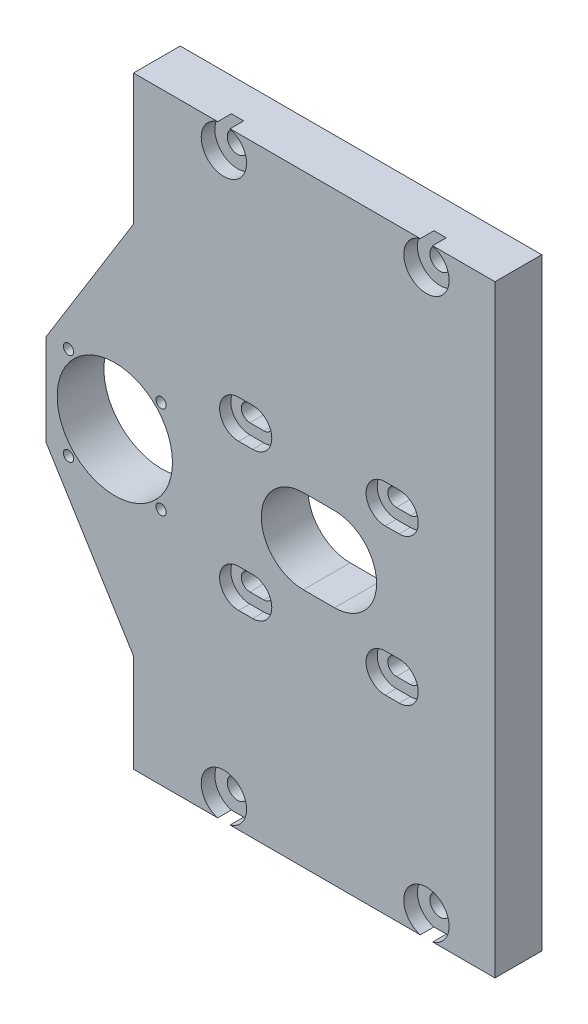
SolidWorks part; units mm, degrees
ref_plane "Front Plane" through (0, 0, 0) normal (0, 0, 1) x (1, 0, 0)
ref_plane "Top Plane" through (0, 0, 0) normal (0, 1, 0) x (1, 0, 0)
ref_plane "Right Plane" through (0, 0, 0) normal (1, 0, 0) x (0, 0, -1)
sketch "Sketch1" plane through (0, 0, 0) normal (0, 0, 1) x (1, 0, 0)
  line L24 (-148, 255) -> (-148, 190) construction
  line L31 (-148, 70) -> (-148, 10) construction
  line L32 (-148, 38.5) -> (-32, 38.5) construction
  line L36 (-32, 232) -> (-148, 232) construction
  line L37 (-148, 232) -> (-148, 190)
  line L38 (-148, 70) -> (-148, 38.5)
  line L39 (-148, 38.5) -> (-32, 38.5)
  line L43 (-32, 232) -> (-148, 232)
  line L44 (-176, 115.2267) -> (-176, 144.7733) construction
  line L45 (-176, 115.2267) -> (-176, 144.7733)
  line L46 (-176, 144.7733) -> (-148, 190)
  line L47 (-176, 115.2267) -> (-148, 70)
  line L51 (-32, 38.5) -> (-32, 232)
  circle A8 centre (-154, 130) radius 18.5
  circle A9 centre (-154, 130) radius 18.5
  dimension "D1" = 0.5
extrude "Boss-Extrude1" add sketch "Sketch1" along normal blind 15
sketch "Sketch2" plane through (0, 0, 15) normal (0, 0, 1) x (1, 0, 0)
  circle A1 centre (-139.1508, 115.1508) radius 2.25
  circle A3 centre (-168.8492, 115.1508) radius 2.25
  circle A5 centre (-168.8492, 144.8492) radius 2.25
  circle A7 centre (-139.1508, 144.8492) radius 2.25
hole_wizard "M4x0.7 Tapped Hole1" positions "Sketch3" profile "Sketch4" tap size "M4x0.7" standard "ANSI Metric"
sketch "Sketch3" plane through (0, 0, 15) normal (0, 0, 1) x (1, 0, 0)
  point P0 (-168.8492, 144.8492)
  point P3 (-139.1508, 144.8492)
  point P6 (-139.1508, 115.1508)
  point P9 (-168.8492, 115.1508)
sketch "Sketch4" plane through (-168.8492, 144.8492, 15) normal (1, 0, 0) x (0, -1, 0)
  line L0 (0, 0) -> (0, 14.1)
  line L1 (0, 14.1) -> (1.65, 13.1086)
  line L2 (1.65, 13.1086) -> (1.65, 0)
  line L5 (1.65, 0) -> (0, 0)
  line L10 (0, 14.1) -> (-1.65, 13.1086) construction
  line L11 (0, -6.35) -> (0, 107.95) construction
  dimension "Tap Drill Dia." = 3.3
  dimension "Tap Drill Depth" = 14.1
  dimension "Drill Angle" = 118
cosmetic thread "Hole Thread1" parameters "D1"=12, "D2"=4
cosmetic thread "Hole Thread2" parameters "D1"=12, "D2"=4
cosmetic thread "Hole Thread3" parameters "D1"=12, "D2"=4
cosmetic thread "Hole Thread4" parameters "D1"=12, "D2"=4
hole_wizard "CBORE for M6 Hex Head Bolt1" positions "Sketch5" profile "Sketch6" counterbore size "M6" standard "ANSI Metric"
sketch "Sketch5" plane through (0, 0, 15) normal (0, 0, 1) x (1, 0, 0)
  point P0 (-54, 225)
  point P3 (-119, 225)
  point P6 (-54, 45.5)
  point P9 (-119, 45.5)
sketch "Sketch6" plane through (-54, 225, 15) normal (1, 0, 0) x (0, -1, 0)
  line L0 (0, 0) -> (0, 29.9828)
  line L1 (0, 29.9828) -> (3.3, 28)
  line L2 (3.3, 28) -> (3.3, 4.38)
  line L3 (3.3, 4.38) -> (7.275, 4.38)
  line L4 (7.275, 4.38) -> (7.275, 0)
  line L5 (7.275, 0) -> (0, 0)
  line L10 (0, 29.9828) -> (-3.3, 28) construction
  line L11 (0, -6.35) -> (0, 107.95) construction
  dimension "Hole Dia." = 6.6
  dimension "Hole Depth" = 28
  dimension "C'Bore Dia." = 14.55
  dimension "C'Bore Depth" = 4.38
  dimension "Drill Angle" = 118
sketch "Sketch7" plane through (0, 0, 15) normal (0, 0, 1) x (1, 0, 0)
  line L0 (-83.5, 129.1439) -> (-88.5, 129.1439)
  line L1 (-107, 152.6439) -> (-112, 152.6439)
  line L2 (-60, 152.6439) -> (-65, 152.6439)
  line L3 (-60, 105.6439) -> (-65, 105.6439)
  line L4 (-107, 105.6439) -> (-112, 105.6439)
  circle A1 centre (-60, 105.6439) radius 2.85 construction
  circle A2 centre (-83.5, 129.1439) radius 13.5
  circle A3 centre (-83.5, 129.1439) radius 13.5
  circle A4 centre (-107, 105.6439) radius 2.85 construction
  circle A5 centre (-107, 152.6439) radius 2.85 construction
  circle A6 centre (-60, 152.6439) radius 2.85 construction
  circle A7 centre (-60, 105.6439) radius 2.85
  circle A8 centre (-107, 105.6439) radius 2.85
  circle A9 centre (-107, 152.6439) radius 2.85
  circle A10 centre (-60, 152.6439) radius 2.85
  dimension "D1" = 1
hole_wizard "Ø1.0mm Dowel Slot1" positions "Sketch8" profile "Sketch9" size "Ø1.0" standard "ANSI Metric" slot yes
sketch "Sketch8" plane through (0, 0, 15) normal (0, 0, 1) x (1, 0, 0)
  line L0 (-107, 129.1439) -> (-70, 129.1439) construction
  point P0 (-88.5, 129.1439)
  dimension "D1" = 37
sketch "Sketch9" plane through (-88.5, 129.1439, 15) normal (1, 0, 0) x (0, -1, 0)
  line L0 (0, 0) -> (0, 36.1116)
  line L1 (0, 36.1116) -> (13.5, 28)
  line L2 (13.5, 28) -> (13.5, 0)
  line L5 (13.5, 0) -> (0, 0)
  line L10 (0, 36.1116) -> (-13.5, 28) construction
  line L11 (0, -6.35) -> (0, 107.95) construction
  dimension "Hole Dia." = 27
  dimension "Hole Depth" = 28
  dimension "Drill Angle" = 118
hole_wizard "CBORE SLOT for M5 Hex Head Bolt1" positions "Sketch10" profile "Sketch11" size "M5" standard "ANSI Metric" slot yes
sketch "Sketch10" plane through (0, 0, 15) normal (0, 0, 1) x (1, 0, 0)
  line L0 (-117, 152.6439) -> (-107, 152.6439) construction
  point P0 (-112, 152.6439)
  point P5 (-112, 105.6439)
  point P8 (-65, 152.6439)
  point P11 (-65, 105.6439)
  dimension "D1" = 10
sketch "Sketch11" plane through (-112, 152.6439, 15) normal (1, 0, 0) x (0, -1, 0)
  line L0 (0, 0) -> (0, 29.6524)
  line L1 (0, 29.6524) -> (2.75, 28)
  line L2 (2.75, 28) -> (2.75, 3.58)
  line L3 (2.75, 3.58) -> (6.12, 3.58)
  line L4 (6.12, 3.58) -> (6.12, 0)
  line L5 (6.12, 0) -> (0, 0)
  line L10 (0, 29.6524) -> (-2.75, 28) construction
  line L11 (0, -6.35) -> (0, 107.95) construction
  dimension "Hole Dia." = 5.5
  dimension "Hole Depth" = 28
  dimension "C'Bore Dia." = 12.24
  dimension "C'Bore Depth" = 3.58
  dimension "Drill Angle" = 118
